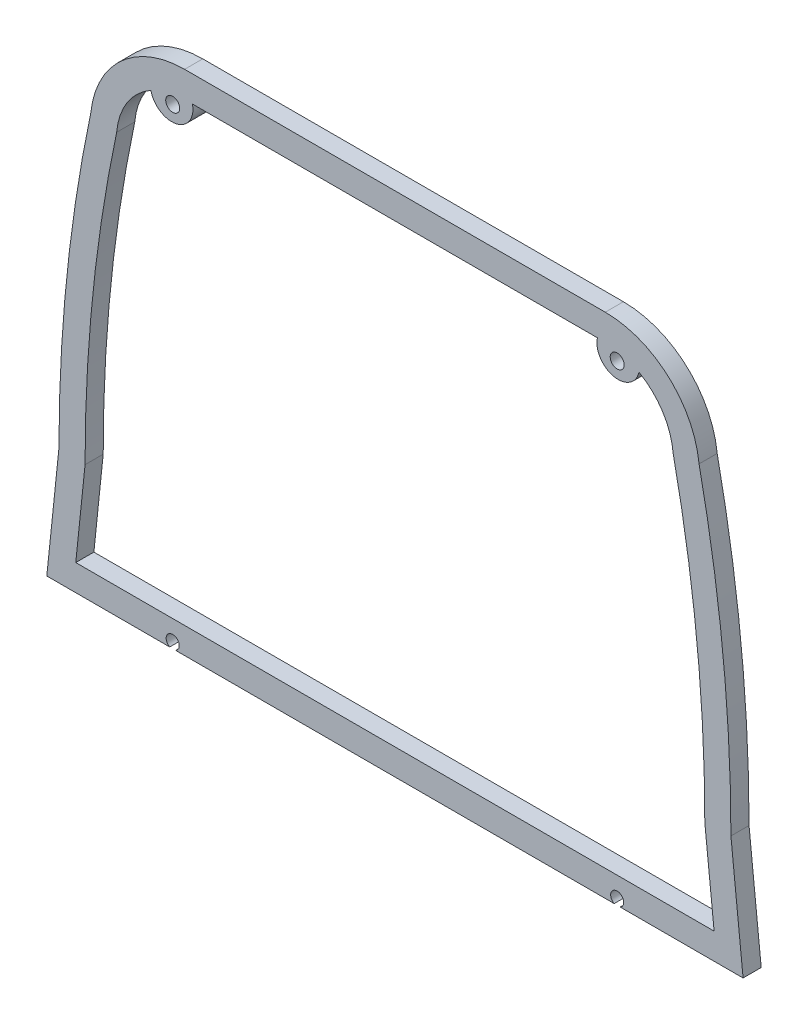
SolidWorks part; units mm, degrees
material "Delrin 2700 NC010, Low Viscosity Acetal Copolymer (SS)"
ref_plane "Front Plane" through (0, 0, 0) normal (0, 0, 1) x (1, 0, 0)
ref_plane "Top Plane" through (0, 0, 0) normal (0, 1, 0) x (1, 0, 0)
ref_plane "Right Plane" through (0, 0, 0) normal (1, 0, 0) x (0, 0, -1)
sketch "Sketch1" plane through (0, 0, 0) normal (0, 0, 1) x (1, 0, 0)
  line L0 (29.4151, -11.9888) -> (30.48, -22.225)
  line L1 (18.415, 22.225) -> (-18.415, 22.225)
  line L2 (-30.48, -22.225) -> (-26.6257, 14.8242) construction
  line L3 (-29.4151, -11.9888) -> (-29.4151, 14.6458) construction
  line L4 (-29.4151, -11.9888) -> (-30.48, -22.225)
  line L5 (18.415, 19.939) -> (-18.415, 19.939)
  line L6 (27.1291, -12.1069) -> (27.9438, -19.939)
  line L7 (-27.9438, -19.939) -> (27.9438, -19.939)
  line L8 (-30.48, -22.225) -> (30.48, -22.225)
  line L9 (-27.1291, -12.1069) -> (-27.9438, -19.939)
  line L18 (0, 18.415) -> (0, -18.415) construction
  line L19 (-1007.9925, 0) -> (48992.0075, 0) construction
  line L24 (-26.797, -2.2098) -> (26.797, -2.2098) construction
  line L25 (-26.797, -2.2098) -> (-26.797, -11.9888) construction
  line L26 (-26.797, -11.9888) -> (26.797, -11.9888) construction
  line L27 (26.797, -2.2098) -> (26.797, -11.9888) construction
  arc A0 (18.415, 22.225) -> (26.6257, 14.8242) centre (18.415, 13.97) cw
  arc A1 (-18.415, 22.225) -> (-26.6257, 14.8242) centre (-18.415, 13.97) ccw
  arc A2 (29.4151, -11.9888) -> (26.6257, 14.8242) centre (-100.8481, -11.9888) ccw
  circle A3 centre (0, -15.748) radius 3.7592 construction
  circle A4 centre (19.4575, -21.717) radius 0.5715
  arc A5 (-29.4151, -11.9888) -> (-26.6257, 14.8242) centre (100.8481, -11.9888) cw
  arc A6 (-27.1291, -12.1069) -> (-24.3623, 14.4786) centre (100.8481, -11.9888) cw
  arc A7 (-21.3655, 19.1588) -> (-17.7253, 19.939) centre (-19.5454, 19.5489) ccw
  arc A8 (21.3655, 19.1588) -> (17.7253, 19.939) centre (19.5454, 19.5489) cw
  circle A9 centre (-19.4575, 19.05) radius 0.6096
  circle A10 centre (19.4575, 19.05) radius 0.6096
  circle A12 centre (-19.4575, -21.717) radius 0.5715
  arc A18 (-18.415, 19.939) -> (-24.3623, 14.4786) centre (-18.415, 13.97) ccw
  arc A19 (18.415, 19.939) -> (24.3623, 14.4786) centre (18.415, 13.97) cw
  arc A20 (27.1291, -12.1069) -> (24.3623, 14.4786) centre (-100.8481, -11.9888) ccw
  point P0 (0, 0)
  point P1 (0, 22.225)
  point P26 (0, -22.225)
  point P31 (0, -11.9888)
  dimension "D4" = 2.286
  dimension "D6" = 8.255
  dimension "D7" = 19.4575
  dimension "D8" = 44.45
  dimension "D9" = 15.748
  dimension "D5" = 1.2192
  dimension "D17" = 1.143
  dimension "D3" = 7.5184
  dimension "D2" = 36.83
  dimension "D10" = 21.717
  dimension "D11" = 19.05
  dimension "D12" = 60.96
  dimension "D13" = 19.4575
  dimension "D14" = 22.225
  dimension "D15" = 53.594
  dimension "D16" = 9.779
extrude "Boss-Extrude1" add sketch "Sketch1" along normal blind 1.5875 contours L8 A12 A4 L0 A2 A0 L1 A1 A5 L4 A20 L6 L7 L9 A6 A18 L5 A19 | L5 A18 A7 A9 | A19 L5 A8 A10 region at (29.1972, -17.185, 0) region at (19.9299, 19.6989, 0) region at (-19.1643, 17.771, 0)
ref_axis "Axis1" through (0, -15.748, 0) along (0, 0, 1)
